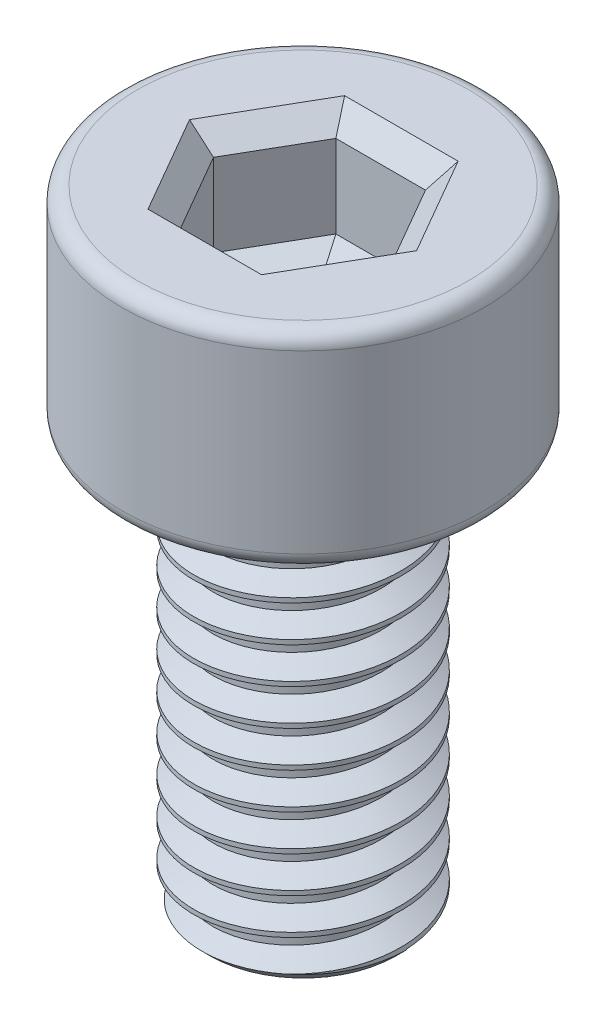
SolidWorks part; units mm, degrees
material "AISI 1020"
ref_plane "Front Plane" through (0, 0, 0) normal (0, 0, 1) x (1, 0, 0)
ref_plane "Top Plane" through (0, 0, 0) normal (0, 1, 0) x (1, 0, 0)
ref_plane "Right Plane" through (0, 0, 0) normal (1, 0, 0) x (0, 0, -1)
sketch "Sketch1" plane through (0, 0, 0) normal (0, 1, 0) x (1, 0, 0)
  circle A0 centre (0, 0) radius 3.5
  dimension "D1" = 7
extrude "Boss-Extrude1" add sketch "Sketch1" along normal blind 4
sketch "Sketch2" plane through (0, 4, 0) normal (0, 1, 0) x (1, 0, 0)
  line L1 (1.7321, 0) -> (0.866, 1.5)
  line L2 (0.866, 1.5) -> (-0.866, 1.5)
  line L3 (-0.866, 1.5) -> (-1.7321, 0)
  line L4 (-1.7321, 0) -> (-0.866, -1.5)
  line L5 (-0.866, -1.5) -> (0.866, -1.5)
  line L6 (0.866, -1.5) -> (1.7321, 0)
  circle A0 centre (0, 0) radius 1.5 construction
  dimension "D1" = 3
extrude "Cut-Extrude1" cut sketch "Sketch2" against normal blind 2
sketch "Sketch5" plane through (0, 2, 0) normal (0, 1, 0) x (1, 0, 0)
  line L6 (0.866, -1.5) -> (1.7321, 0)
  line L7 (1.7321, 0) -> (0.866, 1.5)
  line L8 (0.866, 1.5) -> (-0.866, 1.5)
  line L9 (-0.866, 1.5) -> (-1.7321, 0)
  line L10 (-1.7321, 0) -> (-0.866, -1.5)
  line L11 (-0.866, -1.5) -> (0.866, -1.5)
  line L12 (0.866, -1.5) -> (1.7321, 0)
  line L13 (1.7321, 0) -> (0.866, 1.5)
  line L14 (0.866, 1.5) -> (-0.866, 1.5)
  line L15 (-0.866, 1.5) -> (-1.7321, 0)
  line L16 (-1.7321, 0) -> (-0.866, -1.5)
  line L17 (-0.866, -1.5) -> (0.866, -1.5)
  dimension "D1" = 0
extrude "Cut-Extrude2" cut sketch "Sketch5" against normal blind 1 draft 70
sketch "Sketch6" plane through (0, 0, 0) normal (0, -1, 0) x (1, 0, 0)
  circle A0 centre (0, 0) radius 2
  dimension "D1" = 4
extrude "Boss-Extrude2" add sketch "Sketch6" along normal blind 8
chamfer "Chamfer1" distance 0.4 angle 45 6 edges at (0, 4, 1.5) (-1.299, 4, 0.75) (-1.299, 4, -0.75) (0, 4, -1.5) (1.299, 4, -0.75) (1.299, 4, 0.75)
fillet "Fillet1" radius 0.3 2 edges at (0, 0, 3.5) (0, 4, 3.5)
fillet "Fillet2" radius 0.15 1 edges at (0, 0, -2)
thread "Thread1" pitch 0.7 start angle 0, offset 0.4, length 0, pitch 0.7, diameter 4
ref_plane "Plane1" through (2, -8.4, 0) normal (0, 0, 1) x (1, 0, 0)
sketch "Thread Profile1" plane through (2, -8.4, 0) normal (0, 0, 1) x (1, 0, 0)
  line L0 (0, 0) -> (0, 0.7) construction
  line L11 (0, 0) -> (0, 0.6125)
  line L12 (0, 0.6125) -> (-0.3789, 0.3937)
  line L13 (-0.3789, 0.3937) -> (-0.3789, 0.2187)
  line L15 (-0.3789, 0.2187) -> (0, 0)
  line L17 (-0.3789, 0.3062) -> (0, 0.3062) construction
  point P2 (0, 0)
  dimension "Pitch" = 0.7
  dimension "Profile_Angle" = 60
  dimension "Profile_Land" = 0.175
  dimension "Profile_Height" = 0.3789
chamfer "Chamfer2" distance 0.2 angle 45 1 edges at (0.4483, -8, 1.9491)
